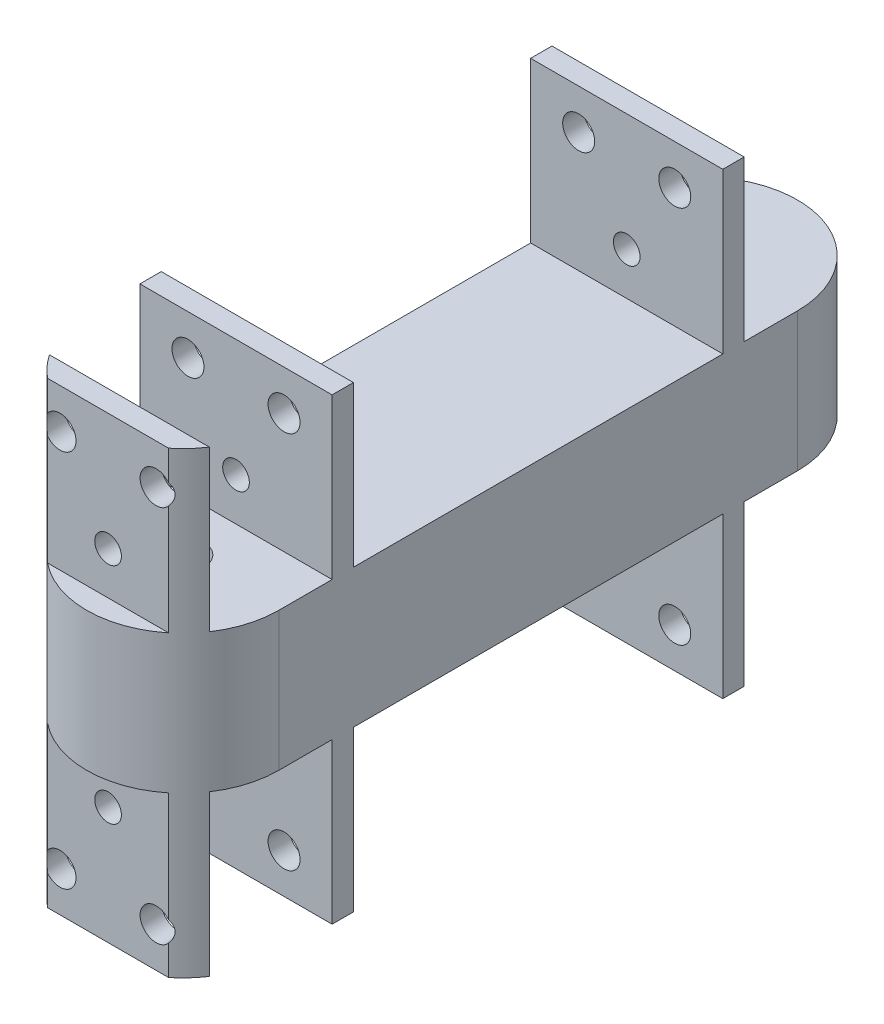
SolidWorks part; units mm, degrees
ref_plane "Front Plane" through (0, 0, 0) normal (0, 0, 1) x (1, 0, 0)
ref_plane "Top Plane" through (0, 0, 0) normal (0, 1, 0) x (1, 0, 0)
ref_plane "Right Plane" through (0, 0, 0) normal (1, 0, 0) x (0, 0, -1)
sketch "Sketch1" plane through (0, 0, 0) normal (0, 1, 0) x (1, 0, 0)
  line L0 (0, 0) -> (0, 97.29) construction
  line L1 (0, 0) -> (0, 97.29) construction
  line L2 (-8.025, 0) -> (-8.025, 97.29) construction
  line L3 (8.025, 0) -> (8.025, 97.29) construction
  line L4 (-18.025, 0) -> (-18.025, 97.29)
  line L5 (18.025, 0) -> (18.025, 97.29)
  line L6 (18.025, 48.645) -> (-18.025, 48.645) construction
  circle A0 centre (0, 0) radius 8.025 construction
  arc A1 (-8.025, 0) -> (8.025, 0) centre (0, 0) ccw construction
  arc A2 (8.025, 97.29) -> (-8.025, 97.29) centre (0, 97.29) ccw construction
  arc A3 (18.025, 97.29) -> (-18.025, 97.29) centre (0, 97.29) ccw
  arc A4 (-18.025, 0) -> (18.025, 0) centre (0, 0) ccw
  circle A5 centre (0, 0) radius 4
  circle A6 centre (0, 97.29) radius 4
  point P3 (0, 48.645)
  dimension "D1" = 16.05
  dimension "D4" = 8
  dimension "D2" = 97.29
  dimension "D3" = 10
extrude "Boss-Extrude1" add sketch "Sketch1" along normal blind 3
sketch "Sketch3" plane through (0, 3, 0) normal (0, 1, 0) x (1, 0, 0)
  line L1 (-15.025, 0) -> (-18.025, 0)
  line L2 (15.025, 0) -> (15.025, 97.29)
  line L3 (18.025, 0) -> (18.025, 97.29)
  line L4 (0, 97.011) -> (0, 112.315) construction
  line L5 (0, 112.315) -> (0, 115.315)
  arc A2 (15.025, 97.29) -> (-15.025, 97.29) centre (0, 97.29) ccw
  arc A3 (15.025, 97.29) -> (0, 112.315) centre (0, 97.29) ccw
  arc A4 (0, 115.315) -> (18.025, 97.29) centre (0, 97.29) cw
  arc A5 (-15.025, 0) -> (15.025, 0) centre (0, 0) ccw
  arc A6 (-15.025, 0) -> (15.025, 0) centre (0, 0) ccw
  arc A7 (-18.025, 0) -> (18.025, 0) centre (0, 0) ccw
  arc A8 (18.025, 97.29) -> (-18.025, 97.29) centre (0, 97.29) ccw construction
  point P4 (0, 0)
  dimension "D1" = 3
  dimension "D2" = 3
extrude "Boss-Extrude3" add sketch "Sketch3" along normal blind 20
ref_plane "Plane1" through (0, 13, 0) normal (0, 1, 0) x (1, 0, 0)
mirror "Mirror1" about plane through (0, 13, 0) normal (0, 1, 0) of "Boss-Extrude1"
sketch "Sketch4" plane through (0, 0, 0) normal (0, -1, 0) x (1, 0, 0)
  line L0 (-18.025, -97.29) -> (-18.025, 0) construction
  line L1 (-18.025, -10) -> (18.025, -10)
  line L2 (-18.025, -10) -> (-18.025, -14)
  line L3 (-18.025, -14) -> (18.025, -14)
  line L4 (18.025, -10) -> (18.025, -14)
  line L5 (18.025, 0) -> (18.025, -97.29) construction
  line L6 (-18.025, 0) -> (18.025, 0) construction
  line L7 (-14.9967, 10) -> (14.9967, 10)
  line L8 (-18.025, 10) -> (18.025, 10) construction
  line L9 (-11.3534, 14) -> (11.3534, 14)
  line L10 (0, 14) -> (0, 10) construction
  line L11 (-18.025, -48.645) -> (18.025, -48.645) construction
  line L12 (-18.025, -83.29) -> (18.025, -83.29)
  line L13 (18.025, -87.29) -> (18.025, -83.29)
  line L14 (-18.025, -87.29) -> (18.025, -87.29)
  line L15 (-18.025, -87.29) -> (-18.025, -83.29)
  arc A0 (18.025, 0) -> (-18.025, 0) centre (0, 0) ccw construction
  arc A1 (11.3534, 14) -> (14.9967, 10) centre (0, 0) cw
  arc A2 (-11.3534, 14) -> (-14.9967, 10) centre (0, 0) ccw
  dimension "D1" = 4
  dimension "D2" = 10
  dimension "D3" = 10
extrude "Boss-Extrude4" add sketch "Sketch4" along normal blind 30
sketch "Sketch5" plane through (0, 0, -14) normal (0, 0, -1) x (-1, 0, 0)
  line L0 (-18.025, 0) -> (0, -8) construction
  line L1 (18.025, -15) -> (-18.025, -15) construction
  line L2 (18.025, -30) -> (18.025, 0) construction
  line L3 (-18.025, -30) -> (-18.025, 0) construction
  line L4 (-18.025, -15) -> (0, -30) construction
  line L5 (18.025, -30) -> (-18.025, -30) construction
  line L6 (0, -30) -> (0, -15) construction
  circle A0 centre (0, -8) radius 2.5
  circle A1 centre (-9.0125, -22.5) radius 3
  circle A2 centre (9.0125, -22.5) radius 3
  dimension "D1" = 5
  dimension "D3" = 6
  dimension "D2" = 8
extrude "Cut-Extrude1" cut sketch "Sketch5" against normal up to surface and the other way up to surface up to face at (0, -15, 14) other way up to face at (0, -15, -87.29)
mirror "Mirror2" about plane through (0, 13, 0) normal (0, 1, 0) of "Cut-Extrude1", "Boss-Extrude4"
